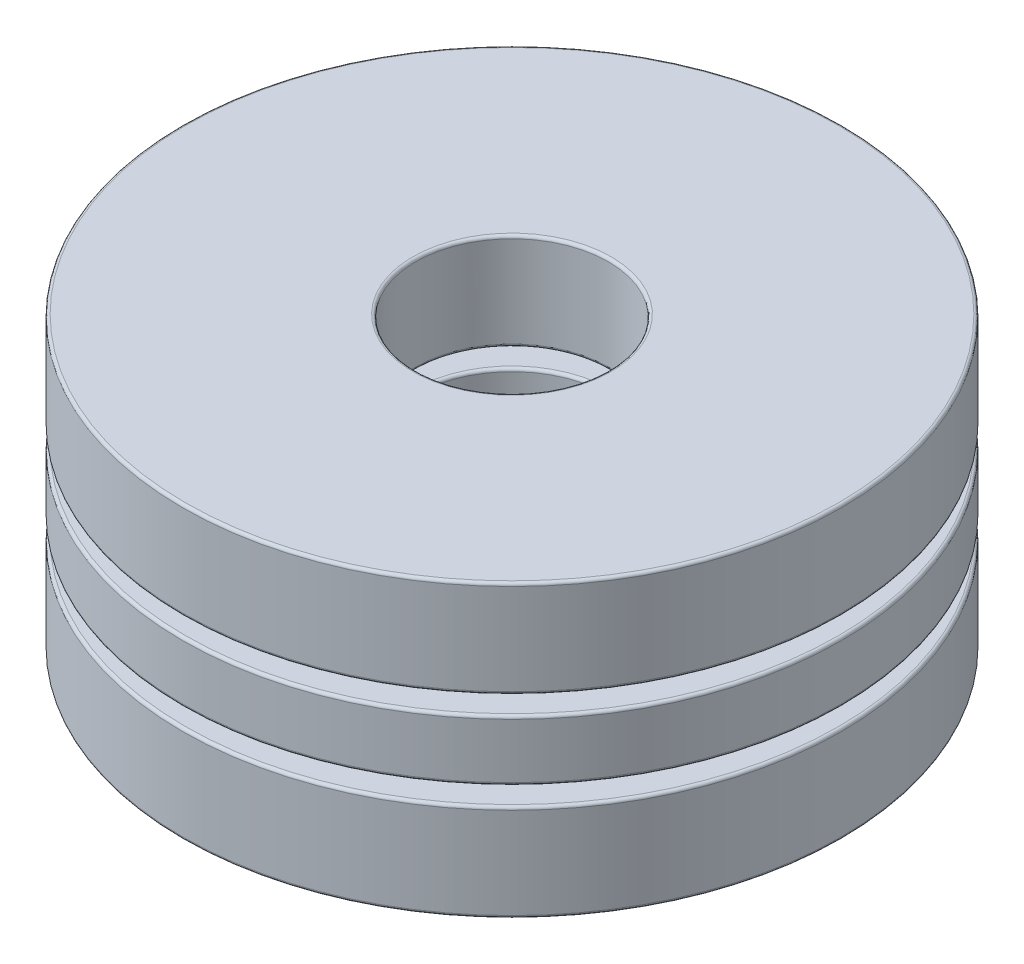
SolidWorks part; units mm, degrees
ref_plane "Front Plane" through (0, 0, 0) normal (0, 0, 1) x (1, 0, 0)
ref_plane "Top Plane" through (0, 0, 0) normal (0, 1, 0) x (1, 0, 0)
ref_plane "Right Plane" through (0, 0, 0) normal (1, 0, 0) x (0, 0, -1)
sketch "Sketch1" plane through (0, 0, 0) normal (1, 0, 0) x (0, 0, -1)
  line L0 (-5.5563, 0) -> (5.5562, 0) construction
  line L1 (0, -2.4511) -> (0, 2.4511) construction
  line L2 (-5.5563, 0.5106) -> (-1.6256, 0.5106)
  line L3 (-5.5563, 0.5106) -> (-5.5563, -0.5106)
  line L4 (-5.5563, -0.5106) -> (-1.6256, -0.5106)
  line L5 (-1.6256, 0.5106) -> (-1.6256, -0.5106)
  line L6 (-3.5909, 0.817) -> (-3.5909, -0.817) construction
  circle A0 centre (-3.5909, 0) radius 0.817 construction
  point P13 (-3.5909, 0.5106)
  dimension "OD" = 11.1125
  dimension "Shaft Dia" = 3.2512
  dimension "Th" = 4.9022
  dimension "D1" = 1.6341
  dimension "D2" = 1.0213
revolve "Revolve1" add sketch "Sketch1" angle 360 about L1
sketch "Sketch3" plane through (0, 0, 0) normal (1, 0, 0) x (0, 0, -1)
  line L0 (-3.5909, 0.817) -> (-3.5909, -0.817)
  arc A0 (-3.5909, 0.817) -> (-3.5909, -0.817) centre (-3.5909, 0) ccw
  circle A1 centre (-3.5909, 0) radius 0.817 construction
revolve "Cut-Revolve1" cut sketch "Sketch3" angle 360 about L0
sketch "Sketch2" plane through (0, 0, 0) normal (1, 0, 0) x (0, 0, -1)
  line L0 (-3.5909, 0.817) -> (-3.5909, -0.817)
  arc A0 (-3.5909, 0.817) -> (-3.5909, -0.817) centre (-3.5909, 0) ccw
  circle A2 centre (-3.5909, 0) radius 0.817 construction
revolve "Revolve2" add sketch "Sketch2" angle 360 about L0
ref_axis "Axis1" through (0, 2.4511, 0) along (0, -1, 0)
pattern_circular "CirPattern1" count 2 every 180 about axis through (0, 2.4511, 0) along (0, -1, 0) of bodies 187
pattern_circular "CirPattern2" count 2 every 180 about axis through (0, 2.4511, 0) along (0, -1, 0) of "Cut-Revolve1"
sketch "Sketch4" plane through (0, 0, 0) normal (1, 0, 0) x (0, 0, -1)
  line L0 (-5.5563, 0.5106) -> (-5.5563, -0.5106) construction
  line L1 (-5.5562, 0.817) -> (-1.6256, 0.817)
  line L2 (-5.5562, 0.817) -> (-5.5563, 2.4511)
  line L3 (-5.5563, 2.4511) -> (-1.6256, 2.4511)
  line L4 (-1.6256, 0.817) -> (-1.6256, 2.4511)
  line L5 (-5.5562, -2.4511) -> (-1.6256, -2.4511)
  line L6 (-5.5562, -2.4511) -> (-5.5562, -0.817)
  line L7 (-5.5562, -0.817) -> (-1.6256, -0.817)
  line L8 (-1.6256, -2.4511) -> (-1.6256, -0.817)
  line L9 (-3.5909, 0.817) -> (-3.5909, -0.817) construction
  line L10 (-1.6256, 0.5106) -> (-1.6256, -0.5106) construction
  line L11 (0, 0) -> (-5.5563, 0) construction
  line L12 (-5.5563, 0) -> (5.5562, 0) construction
  dimension "Ht" = 4.9022
revolve "Revolve3" add sketch "Sketch4" angle 360 about L1
fillet "Fillet1" radius 0.049 4 edges at (0, 0.817, -1.6256) (0, 2.4511, -1.6256) (0, 0.817, -5.5562) (0, 2.4511, -5.5563)
fillet "Fillet2" radius 0.049 4 edges at (0, -0.5106, -1.6256) (0, 0.5106, -1.6256) (0, -0.5106, -5.5563) (0, 0.5106, -5.5563)
fillet "Fillet3" radius 0.049 4 edges at (0, -2.4511, -1.6256) (0, -0.817, -1.6256) (0, -2.4511, -5.5562) (0, -0.817, -5.5562)
equation "\"D1@Sketch1\" = \"Th@Sketch1\"/3"
equation "\"D2@Sketch1\" = \"D1@Sketch1\"*.625"
equation "\"Balls@CirPattern1\" = \"OD@Sketch1\"*5"
equation "\"Angle@CirPattern1\" = 360/\"Balls@CirPattern1\""
equation "\"D1@CirPattern2\" = \"Balls@CirPattern1\""
equation "\"D2@CirPattern2\" = \"Angle@CirPattern1\""
equation "\"D1@Fillet1\" = \"Th@Sketch1\"*.01"
equation "\"D1@Fillet2\" = \"D1@Fillet1\""
equation "\"D1@Fillet3\" = \"D1@Fillet1\""
